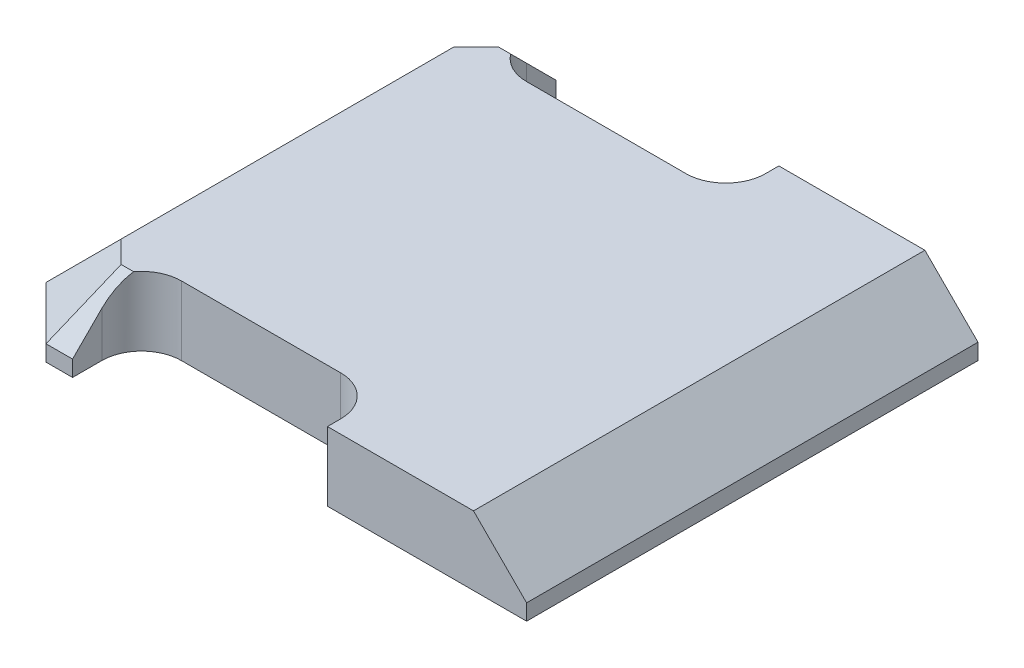
SolidWorks part; units mm, degrees
material "ABS"
ref_plane "Front Plane" through (0, 0, 0) normal (0, 0, 1) x (1, 0, 0)
ref_plane "Top Plane" through (0, 0, 0) normal (0, 1, 0) x (1, 0, 0)
ref_plane "Right Plane" through (0, 0, 0) normal (1, 0, 0) x (0, 0, -1)
sketch "Sketch1" plane through (0, 0, 0) normal (0, 1, 0) x (1, 0, 0)
  line L1 (-97.5, 85) -> (97.5, 85)
  line L2 (-97.5, 85) -> (-97.5, -85)
  line L3 (-97.5, -85) -> (97.5, -85)
  line L4 (97.5, 85) -> (97.5, -85)
  line L5 (-97.5, 85) -> (97.5, -85) construction
  line L6 (-97.5, -85) -> (97.5, 85) construction
  point P0 (0, 0)
  dimension "D1" = 195
  dimension "D2" = 170
extrude "Boss-Extrude1" add sketch "Sketch1" along normal blind 26
sketch "Sketch2" plane through (0, 26, 0) normal (0, 1, 0) x (1, 0, 0)
  line L0 (-97.5, -85) -> (-67.5, -85) construction
  line L1 (-97.5, -85) -> (97.5, -85) construction
  line L2 (0, 0) -> (-97.5, 0) construction
  line L3 (-67.5, -85) -> (22.5, -85)
  line L4 (-67.5, -85) -> (-67.5, -65)
  line L5 (-67.5, -65) -> (22.5, -65)
  line L6 (22.5, -85) -> (22.5, -65)
  line L7 (-97.5, 85) -> (-97.5, -85) construction
  line L8 (-67.5, 65) -> (22.5, 65)
  line L9 (22.5, 85) -> (22.5, 65)
  line L10 (-67.5, 85) -> (22.5, 85)
  line L11 (-67.5, 85) -> (-67.5, 65)
  dimension "D1" = 30
  dimension "D2" = 90
  dimension "D3" = 20
extrude "Cut-Extrude1" cut sketch "Sketch2" against normal through all
fillet "Fillet1" radius 15 4 edges at (22.5, 13, -65) (-67.5, 13, -65) (-67.5, 13, 65) (22.5, 13, 65)
sketch "Sketch3" plane through (0, 26, 0) normal (0, 1, 0) x (1, 0, 0)
  line L0 (0, 0) -> (-97.5, 0) construction
  line L1 (-67.5, 85) -> (-97.5, 85)
  line L2 (-67.5, 85) -> (-67.5, 91)
  line L3 (-67.5, 91) -> (-97.5, 91)
  line L4 (-97.5, 85) -> (-97.5, 91)
  line L5 (-97.5, 85) -> (-97.5, -85) construction
  line L6 (-67.5, -91) -> (-97.5, -91)
  line L7 (-97.5, -85) -> (-97.5, -91)
  line L8 (-67.5, -85) -> (-97.5, -85)
  line L9 (-67.5, -85) -> (-67.5, -91)
  dimension "D1" = 6
extrude "Boss-Extrude2" add sketch "Sketch3" against normal up to surface (26 mm away) up to face at (-16.875, 0, 0)
chamfer "Chamfer1" distance 20 angle 45 2 edges at (-97.5, 13, 91) (-97.5, 13, -91)
chamfer "Chamfer2" distance 20 angle 45 5 edges at (-72.5, 26, 91) (-72.5, 26, -91) (-97.5, 26, 0) (-87.5, 26, 81) (-87.5, 26, -81)
chamfer "Chamfer3" distance 20 angle 45 1 edges at (97.5, 26, 0)
